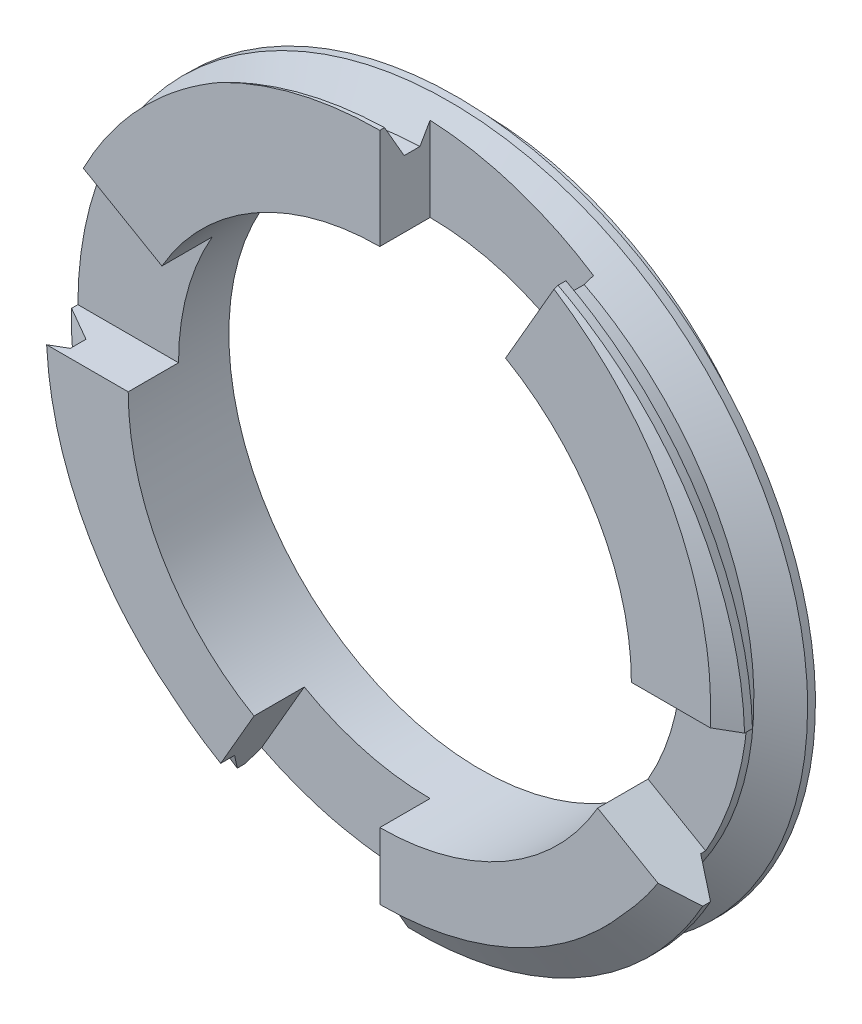
SolidWorks part; units mm, degrees
ref_plane "Front Plane" through (0, 0, 0) normal (1, 0, 0) x (0, 1, 0)
ref_plane "Top Plane" through (0, 0, 0) normal (0, 0, 1) x (0, 1, 0)
ref_plane "Right Plane" through (0, 0, 0) normal (0, 1, 0) x (-1, 0, 0)
sketch "Sketch1" plane through (0, 0, 0) normal (0, 0, 1) x (0, 1, 0)
  circle A0 centre (0, 0) radius 7
extrude "Boss-Extrude1" add sketch "Sketch1" along normal blind 2
sketch "Sketch2" plane through (0, 0, 2) normal (0, 0, 1) x (1, 0, 0)
  circle A0 centre (0, 0) radius 5
extrude "Cut-Extrude1" cut sketch "Sketch2" against normal blind 2
sketch "Sketch5" plane through (0, 0, 2) normal (0, 0, 1) x (1, 0, 0)
  line L0 (0, 7) -> (0, 5)
  line L1 (3.5, 6.0622) -> (2.5, 4.3301)
  line L2 (7, 0) -> (5, 0)
  line L3 (6.0622, -3.5) -> (4.3301, -2.5)
  line L4 (0, -7) -> (0, -5)
  line L5 (-3.5, -6.0622) -> (-2.5, -4.3301)
  line L6 (-7, 0) -> (-5, 0)
  line L7 (-6.0622, 3.5) -> (-4.3301, 2.5)
  arc A0 (0, 7) -> (3.5, 6.0622) centre (0, 0) cw
  circle A1 centre (0, 0) radius 7 construction
  circle A2 centre (0, 0) radius 5 construction
  arc A3 (0, 5) -> (2.5, 4.3301) centre (0, 0) cw
  arc A4 (5, 0) -> (4.3301, -2.5) centre (0, 0) cw
  arc A5 (7, 0) -> (6.0622, -3.5) centre (0, 0) cw
  arc A6 (0, -5) -> (-2.5, -4.3301) centre (0, 0) cw
  arc A7 (0, -7) -> (-3.5, -6.0622) centre (0, 0) cw
  arc A8 (-5, 0) -> (-4.3301, 2.5) centre (0, 0) cw
  arc A9 (-7, 0) -> (-6.0622, 3.5) centre (0, 0) cw
  point P29 (0, 0)
  dimension "D1" = 4
extrude "Cut-Extrude2" cut sketch "Sketch5" against normal blind 1
thread "Thread2" pitch 1.25 method cut profile "Thread Profile2" start angle 0, offset 2, length 5, pitch 1.25, diameter 14
ref_plane "Plane2" through (7, 0, -2) normal (0, -1, 0) x (1, 0, 0)
sketch "Thread Profile2" plane through (7, 0, -2) normal (0, -1, 0) x (1, 0, 0)
  line L0 (0, 0) -> (0, 1.25) construction
  line L11 (0, 0) -> (0, 1.0937)
  line L12 (0, 1.0937) -> (-0.6766, 0.7031)
  line L13 (-0.6766, 0.7031) -> (-0.6766, 0.3906)
  line L15 (-0.6766, 0.3906) -> (0, 0)
  line L17 (-0.6766, 0.5469) -> (0, 0.5469) construction
  point P2 (0, 0)
  dimension "Pitch" = 1.25
  dimension "Profile_Angle" = 60
  dimension "Profile_Land" = 0.3125
  dimension "Profile_Height" = 0.6766
